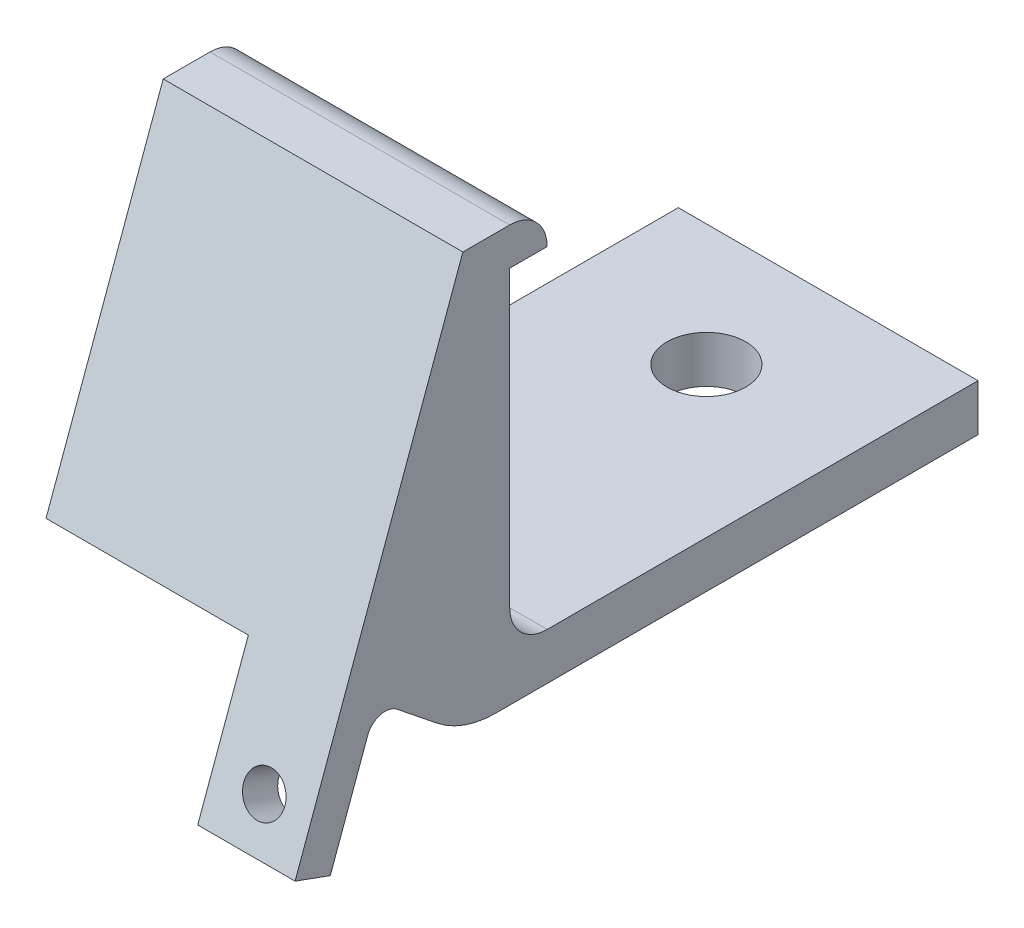
SolidWorks part; units mm, degrees
ref_plane "前视基准面" through (0, 0, 0) normal (0, 0, 1) x (1, 0, 0)
ref_plane "上视基准面" through (0, 0, 0) normal (0, 1, 0) x (1, 0, 0)
ref_plane "右视基准面" through (0, 0, 0) normal (1, 0, 0) x (0, 0, -1)
other "Configuration Table"
sketch "草图1" plane through (0, 0, 0) normal (0, 1, 0) x (1, 0, 0)
  line L0 (0, 0) -> (0, 25)
  line L1 (0, 25) -> (16, 25)
  line L2 (16, 25) -> (16, 0)
  line L3 (16, 0) -> (0, 0)
  line L4 (0, 0) -> (0, -2.5)
  line L5 (0, -2.5) -> (16, -2.5)
  line L6 (16, -2.5) -> (16, 0)
  circle A0 centre (8, 18.5) radius 2.1
  dimension "D4" = 4.2
  dimension "D1" = 25
  dimension "D2" = 16
  dimension "D3" = 18.5
  dimension "D5" = 2.5
  dimension "D7" = 8
extrude "凸台-拉伸1" add sketch "草图1" along normal blind 2.5 contours L3 L2 L1 L0 A0 region at (8, 0, -12.2847)
extrude "凸台-拉伸2" add sketch "草图1<3>" along normal blind 22.2 contours L5 L6 L3 L4 region at (8, 0, 1.25)
sketch "草图1<3>" plane through (0, 0, 0) normal (0, 1, 0) x (1, 0, 0) same geometry as "草图1"
sketch "草图2" plane through (0, 0, 0) normal (0, 0, -1) x (-1, 0, 0)
  line L0 (-16, 22.2) -> (-16, 20.2)
  line L1 (-16, 22.2) -> (-16, 2.5) construction
  line L2 (-16, 20.2) -> (0, 20.2)
  line L3 (0, 22.2) -> (0, 2.5) construction
  line L4 (0, 20.2) -> (0, 22.2)
  line L5 (0, 22.2) -> (-16, 22.2)
  dimension "D1" = 2
extrude "凸台-拉伸3" add sketch "草图2" along normal blind 2
sketch "草图3" plane through (0, 0, 0) normal (-1, 0, 0) x (0, 0, 1)
  line L0 (2.5, 22.2) -> (8.7558, 5.0124)
  line L1 (8.7558, 5.0124) -> (2.5, 0)
  line L4 (2.5, 0) -> (2.5, 22.2)
  dimension "D1" = 18.2907
  dimension "D2" = 20
extrude "凸台-拉伸4" add sketch "草图3" against normal up to surface (16 mm away) contours L0 region at (0, 9.0708, 4.5853) up to face at (16, 11.225, -6.125)
fillet "圆角1" radius 2 2 edges at (8, 2.5, 0) (8, 22.2, -2)
sketch "草图4" plane through (0, 3.4004, 9.3425) normal (0, 0.342, 0.9397) x (1, 0, 0)
  line L2 (16, 1.7154) -> (0, 1.7154) construction
  line L3 (16, 1.7154) -> (0, 1.7154)
  line L5 (16, 1.7154) -> (16, -6.1846)
  line L6 (16, -6.1846) -> (10.8012, -6.1846)
  line L7 (10.8012, -6.1846) -> (10.8012, 1.7154)
  circle A0 centre (13.5, -3.6846) radius 1.1
  line M10 (0, 1.7154) -> (16, 1.7154)
  dimension "D5" = 2.2
  dimension "D1" = 7.9
  dimension "D2" = 5.1988
  dimension "D3" = 2.5
  dimension "D4" = 2.5
extrude "凸台-拉伸5" add sketch "草图4" against normal blind 2 contours M10 | L7 L6 L5 A0 region at (13.3905, 1.4395, 10.0562)
fillet "圆角4" radius 1 1 edges at (13.4006, 3.6921, 7.108)
fillet "圆角5" radius 5 1 edges at (8, 0, 2.5)
